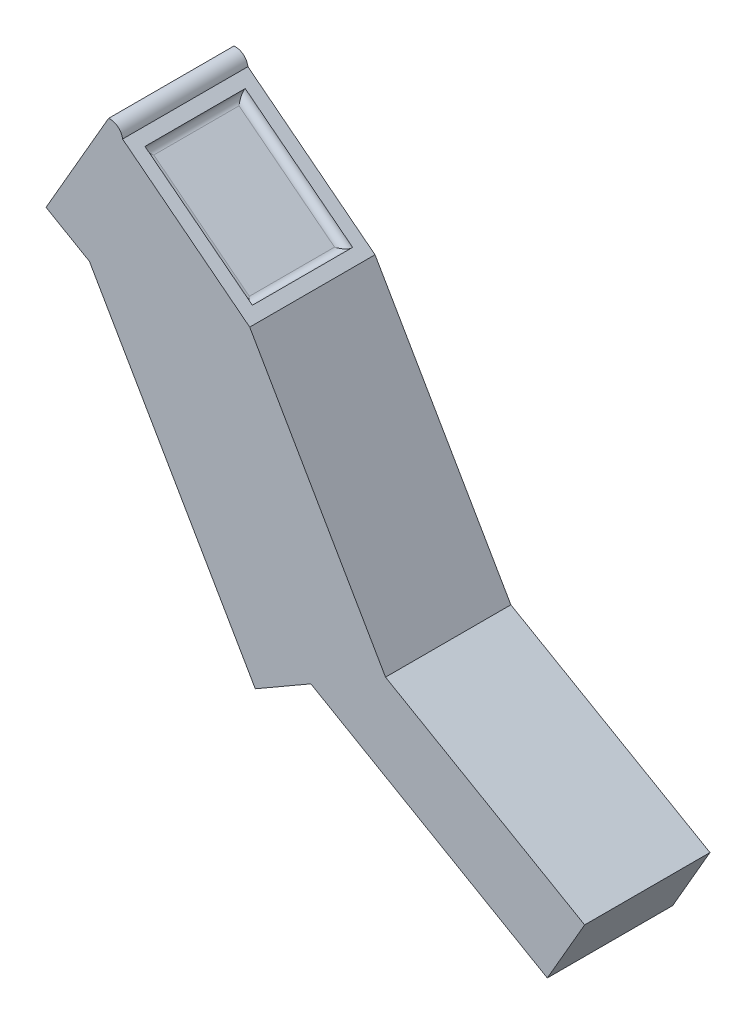
SolidWorks part; units mm, degrees
ref_plane "前视基准面" through (0, 0, 0) normal (0, 0, 1) x (1, 0, 0)
ref_plane "上视基准面" through (0, 0, 0) normal (0, 1, 0) x (1, 0, 0)
ref_plane "右视基准面" through (0, 0, 0) normal (1, 0, 0) x (0, 0, -1)
sketch "草图1" plane through (0, 0, 0) normal (0, 0, 1) x (1, 0, 0)
  line L0 (-6.1272, -2.2012) -> (-3.6317, 2.1211)
  line L1 (-4.3951, -3.2012) -> (0.0043, -5.7412) construction
  line L2 (1.999, -2.2761) -> (-3.0735, 1.6852)
  line L3 (6.2884, -9.7056) -> (7.4181, -11.6623)
  line L5 (0.0043, -5.7412) -> (2.2202, -1.9031) construction
  line L6 (2.2219, -14.6623) -> (-4.3951, -3.2012)
  line L7 (-4.3951, -3.2012) -> (-6.1272, -2.2012)
  line L8 (1.999, -2.2761) -> (6.2884, -9.7056)
  line L9 (2.2219, -14.6623) -> (7.4181, -11.6623)
  arc A0 (-3.6317, 2.1211) -> (-3.0735, 1.6852) centre (-3.5706, 1.624) cw
  dimension "D1" = 150
  dimension "D2" = 2
  dimension "D3" = 8.5788
  dimension "D4" = 13.2341
  dimension "D5" = 5.08
extrude "凸台-拉伸1" add sketch "草图1" along normal blind 5
sketch "草图2" plane through (-0.3469, -0.4442, 0) normal (0.6155, 0.7881, 0) x (0.7881, -0.6155, 0)
  line L0 (-2.9596, -0.5) -> (-2.9596, -4.5)
  line L1 (-2.9596, -4.5) -> (2.4764, -4.5)
  line L2 (2.4764, -4.5) -> (2.4764, -0.5)
  line L3 (2.4764, -0.5) -> (-2.9596, -0.5)
  line L4 (2.9764, 0) -> (-3.4596, 0) construction
  line L5 (2.9764, -5) -> (-3.4596, -5) construction
  line L6 (2.9764, -5) -> (2.9764, 0) construction
  line L7 (-3.4596, -5) -> (-3.4596, 0) construction
  dimension "D1" = 0.5
  dimension "D2" = 0.5
  dimension "D3" = 0.5
  dimension "D4" = 0.5
extrude "切除-拉伸1" cut sketch "草图2" against normal blind 0.3
fillet "圆角2" radius 0.3 4 edges at (-2.8641, 1.141, 2.5) (-0.7219, -0.5319, 0.5) (1.4203, -2.2048, 2.5) (-0.7219, -0.5319, 4.5)
sketch "草图3" plane through (0, 0, 5) normal (0, 0, 1) x (1, 0, 0)
  line L0 (2.2219, -14.6623) -> (7.4181, -11.6623) construction
  line L2 (7.4181, -11.6623) -> (15.3621, -16.2487)
  line L3 (4.4389, -13.3823) -> (13.8725, -18.8287)
  line L5 (13.8725, -18.8287) -> (15.3621, -16.2487)
  line L6 (7.4181, -11.6623) -> (4.4389, -13.3823)
  dimension "D1" = 3.44
extrude "凸台-拉伸2" add sketch "草图3" against normal up to surface (5 mm away) up to face at (-0.7855, -4.2973, 0)
